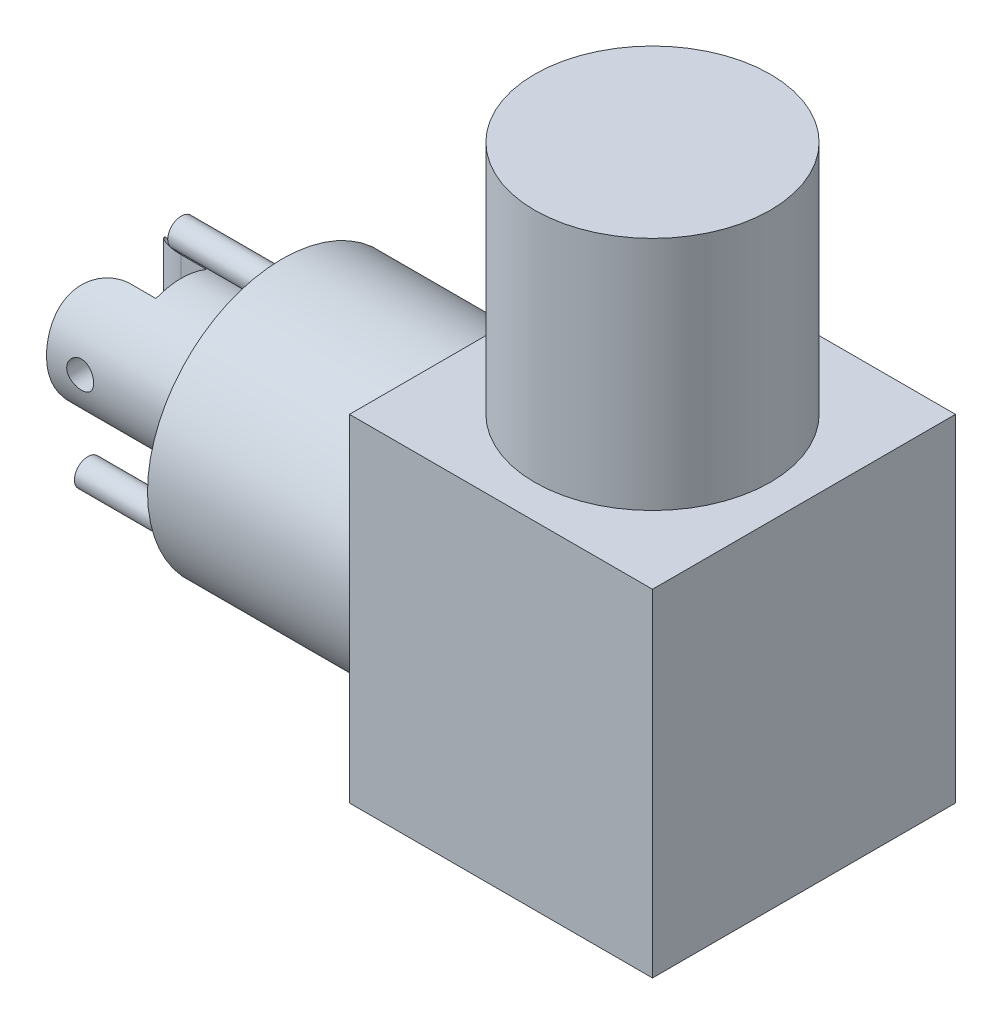
SolidWorks part; units mm, degrees
material "Rubber"
ref_plane "Front Plane" through (0, 0, 0) normal (0, 0, 1) x (1, 0, 0)
ref_plane "Top Plane" through (0, 0, 0) normal (0, 1, 0) x (1, 0, 0)
ref_plane "Right Plane" through (0, 0, 0) normal (1, 0, 0) x (0, 0, -1)
sketch "Sketch2" plane through (0, 0, 0) normal (1, 0, 0) x (0, 0, -1)
  circle A0 centre (0, 0) radius 20
  dimension "D1" = 40
extrude "Boss-Extrude2" add sketch "Sketch2" along normal blind 50
sketch "Sketch3" plane through (0, 0, 0) normal (-1, 0, 0) x (0, 0, 1)
  line L3 (-7.5, 18.5405) -> (-7.5, -18.5405)
  line L4 (7.5, 18.5405) -> (7.5, -18.5405)
  arc A0 (7.5, 18.5405) -> (-7.5, 18.5405) centre (0, 0) ccw
  arc A1 (-7.5, -18.5405) -> (7.5, -18.5405) centre (0, 0) ccw
extrude "Cut-Extrude1" cut sketch "Sketch3" against normal blind 20
fillet "Fillet1" radius 12.5 2 edges at (0, 0, 7.5) (0, 0, -7.5)
sketch "Sketch4" plane through (0, 0, -7.5) normal (0, 0, 1) x (1, 0, 0)
  circle A0 centre (10, 0) radius 4
  dimension "D1" = 8
  dimension "D2" = 10
extrude "Cut-Extrude2" cut sketch "Sketch4" against normal through all and the other way through all
sketch "Sketch5" plane through (50, 0, 0) normal (1, 0, 0) x (0, 0, -1)
  circle A0 centre (0, 0) radius 40
extrude "Boss-Extrude3" add sketch "Sketch5" along normal blind 65
sketch "Sketch7" plane through (50, 0, 0) normal (-1, 0, 0) x (0, 0, 1)
  circle A0 centre (0, 32) radius 4
extrude "Boss-Extrude5" add sketch "Sketch7" along normal blind 30
pattern_circular "CirPattern1" count 3 over 360 about axis through (50, 0, 0) along (1, 0, 0) of "Boss-Extrude5"
sketch "Sketch8" plane through (115, 0, 0) normal (1, 0, 0) x (0, 0, -1)
  line L1 (-45, 55) -> (45, 55)
  line L2 (-45, 55) -> (-45, -45)
  line L3 (-45, -45) -> (45, -45)
  line L4 (45, 55) -> (45, -45)
  point P4 (0, 55)
  dimension "D1" = 90
  dimension "D2" = 100
  dimension "D3" = 45
extrude "Boss-Extrude6" add sketch "Sketch8" along normal blind 90
sketch "Sketch9" plane through (0, 55, 0) normal (0, 1, 0) x (1, 0, 0)
  circle A0 centre (160, 0) radius 35
extrude "Boss-Extrude7" add sketch "Sketch9" along normal blind 70
